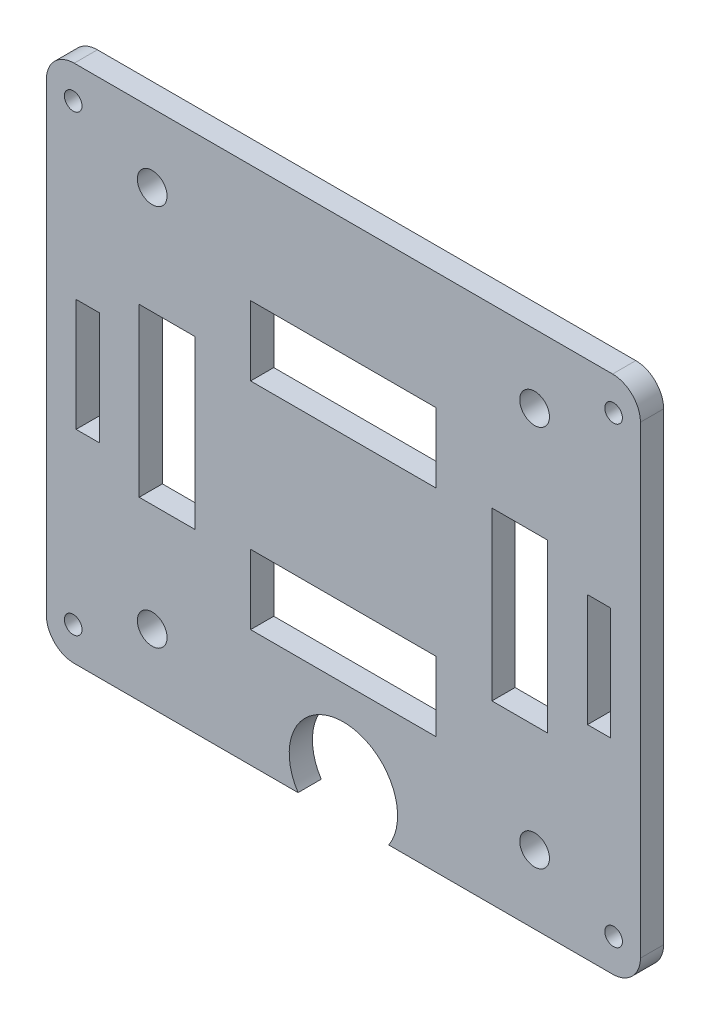
SolidWorks part; units mm, degrees
material "Delrin 2700 NC010, Low Viscosity Acetal Copolymer (SS)"
ref_plane "Front Plane" through (0, 0, 0) normal (0, 0, 1) x (1, 0, 0)
ref_plane "Top Plane" through (0, 0, 0) normal (0, 1, 0) x (1, 0, 0)
ref_plane "Right Plane" through (0, 0, 0) normal (1, 0, 0) x (0, 0, -1)
sketch "Sketch1" plane through (0, 0, 0) normal (0, 0, 1) x (1, 0, 0)
  line L0 (0, -1000) -> (0, 49000) construction
  line L1 (18.415, 17.78) -> (-18.415, 17.78)
  line L2 (20.32, 15.875) -> (20.32, -17.78)
  line L3 (20.32, -17.78) -> (-20.32, -17.78)
  line L4 (-20.32, 15.875) -> (-20.32, -17.78)
  line L5 (20.32, 17.78) -> (-20.32, -17.78) construction
  line L6 (20.32, -17.78) -> (-20.32, 17.78) construction
  line L7 (-1000, 0) -> (49000, 0) construction
  line L8 (-18.288, 3.8505) -> (-16.7005, 3.8505)
  line L9 (10.16, 5.715) -> (13.97, 5.715)
  line L10 (-6.35, -4.9848) -> (6.35, -4.9848)
  line L11 (-6.35, -4.9848) -> (-6.35, -9.7473)
  line L12 (-6.35, -9.7473) -> (6.35, -9.7473)
  line L13 (6.35, -4.9848) -> (6.35, -9.7473)
  line L14 (-6.35, -4.9848) -> (6.35, -9.7473) construction
  line L15 (-16.7005, 3.8505) -> (-16.7005, -3.8505)
  line L16 (-16.7005, -3.8505) -> (-18.288, -3.8505)
  line L17 (-18.288, -3.8505) -> (-18.288, 3.8505)
  line L18 (0, 0) -> (-24.2469, 20.3456) construction
  line L19 (-6.35, -9.7473) -> (6.35, -4.9848) construction
  line L20 (-10.16, 5.715) -> (-13.97, 5.715)
  line L21 (-10.16, 5.715) -> (-10.16, -5.715)
  line L22 (16.7005, -3.8505) -> (18.288, -3.8505)
  line L23 (18.288, -3.8505) -> (18.288, 3.8505)
  line L24 (18.288, 3.8505) -> (16.7005, 3.8505)
  line L25 (16.7005, 3.8505) -> (16.7005, -3.8505)
  line L26 (-10.16, -5.715) -> (-13.97, -5.715)
  line L27 (-13.97, 5.715) -> (-13.97, -5.715)
  line L28 (-10.16, 5.715) -> (-13.97, -5.715) construction
  line L29 (-10.16, -5.715) -> (-13.97, 5.715) construction
  line L30 (10.16, -5.715) -> (13.97, -5.715)
  line L31 (13.97, 5.715) -> (13.97, -5.715)
  line L32 (10.16, 5.715) -> (10.16, -5.715)
  line L33 (-6.35, 4.9848) -> (-6.35, 9.7473)
  line L34 (-6.35, 4.9848) -> (6.35, 4.9848)
  line L35 (-6.35, 9.7473) -> (6.35, 9.7473)
  line L36 (6.35, 4.9848) -> (6.35, 9.7473)
  circle A0 centre (0, -15.748) radius 3.7084
  circle A1 centre (-18.4847, 15.5105) radius 0.6032
  circle A2 centre (-13.08, -13.08) radius 1.016
  circle A3 centre (18.4847, 15.5105) radius 0.6033
  circle A4 centre (-13.08, 13.08) radius 1.016
  circle A5 centre (13.08, 13.08) radius 1.016
  circle A6 centre (13.08, -13.08) radius 1.016
  arc A7 (18.415, -17.78) -> (20.32, -15.875) centre (18.415, -15.875) ccw
  arc A8 (-18.415, -17.78) -> (-20.32, -15.875) centre (-18.415, -15.875) cw
  arc A9 (-18.415, 17.78) -> (-20.32, 15.875) centre (-18.415, 15.875) ccw
  arc A10 (18.415, 17.78) -> (20.32, 15.875) centre (18.415, 15.875) cw
  circle A11 centre (18.4847, -15.5105) radius 0.6033
  circle A12 centre (-18.4847, -15.5105) radius 0.6032
  point P0 (0, 0)
  point P9 (0, 0)
  point P11 (0, -7.366)
  point P49 (18.288, 0)
  point P53 (-12.065, 0)
  dimension "D6" = 7.4168
  dimension "D7" = 1.2065
  dimension "D9" = 2.032
  dimension "D14" = 1.905
  dimension "D15" = 1.905
  dimension "D1" = 35.56
  dimension "D2" = 40.64
  dimension "D3" = 4.7625
  dimension "D4" = 12.7
  dimension "D5" = 15.748
  dimension "D8" = 24.13
  dimension "D10" = 13.08
  dimension "D11" = 13.08
  dimension "D17" = 7.701
  dimension "D18" = 16.7005
  dimension "D16" = 1.5875
  dimension "D19" = 40
  dimension "D20" = 8.382
  dimension "D21" = 3.81
  dimension "D22" = 11.43
  dimension "D23" = 12.065
extrude "Boss-Extrude1" add sketch "Sketch1" along normal blind 1.5875 contours A10 L1 A9 L4 L3 A0 L2 A6 A5 A4 L12 A1 A2 A3 region at (0, 0.4715, 0)
ref_axis "Axis1" through (0, 0, 0) along (0, 0, 1)
